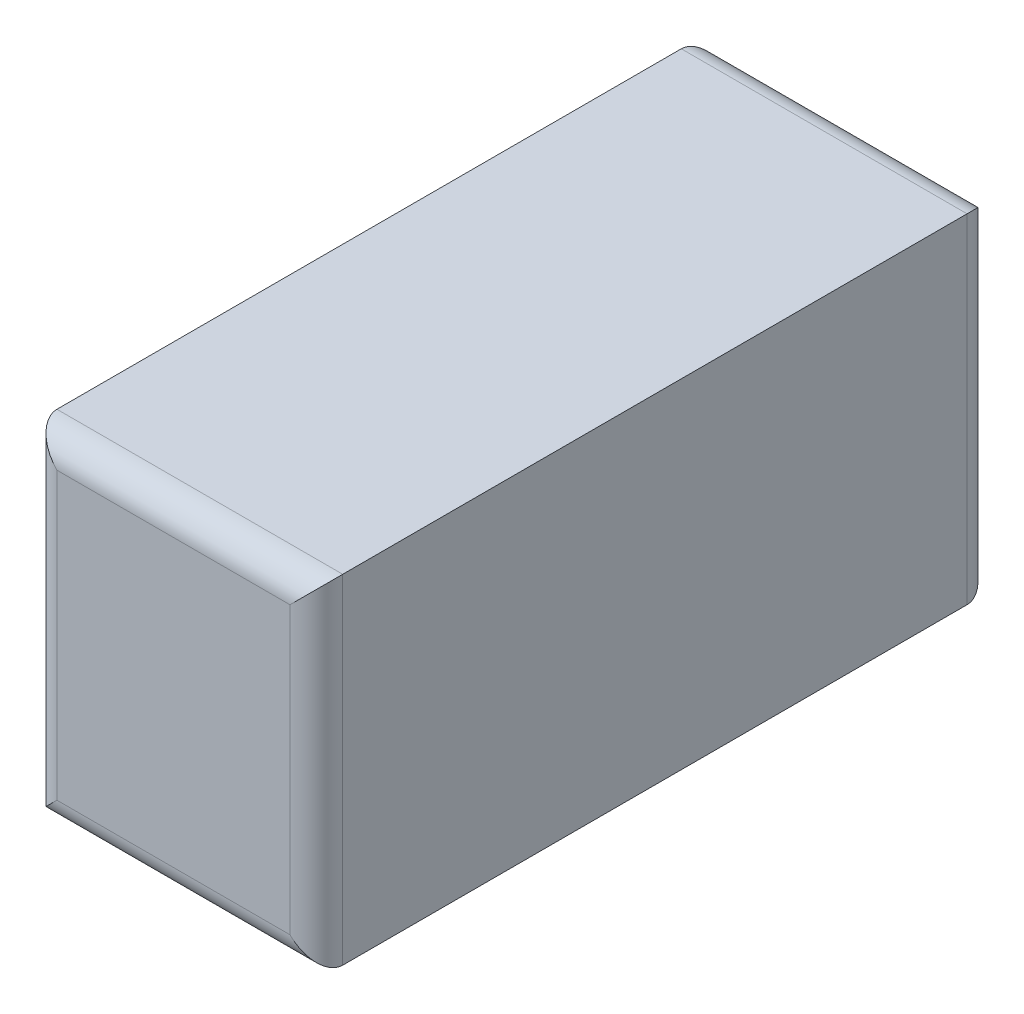
SolidWorks part; units mm, degrees
ref_plane "Front Plane" through (0, 0, 0) normal (0, 0, 1) x (1, 0, 0)
ref_plane "Top Plane" through (0, 0, 0) normal (0, 1, 0) x (1, 0, 0)
ref_plane "Right Plane" through (0, 0, 0) normal (1, 0, 0) x (0, 0, -1)
sketch "Sketch1" plane through (0, 0, 0) normal (0, 0, 1) x (1, 0, 0)
  line L1 (0, 0) -> (32.5, 0)
  line L2 (0, 0) -> (0, 38.5)
  line L3 (0, 38.5) -> (32.5, 38.5)
  line L4 (32.5, 0) -> (32.5, 38.5)
  dimension "D1" = 38.5
  dimension "D2" = 32.5
extrude "Boss-Extrude1" add sketch "Sketch1" along normal blind 77
fillet "Fillet1" radius 3 8 edges at (16.25, 38.5, 77) (32.5, 19.25, 77) (16.25, 0, 77) (0, 19.25, 77) (16.25, 0, 0) (32.5, 19.25, 0) (16.25, 38.5, 0) (0, 19.25, 0)
